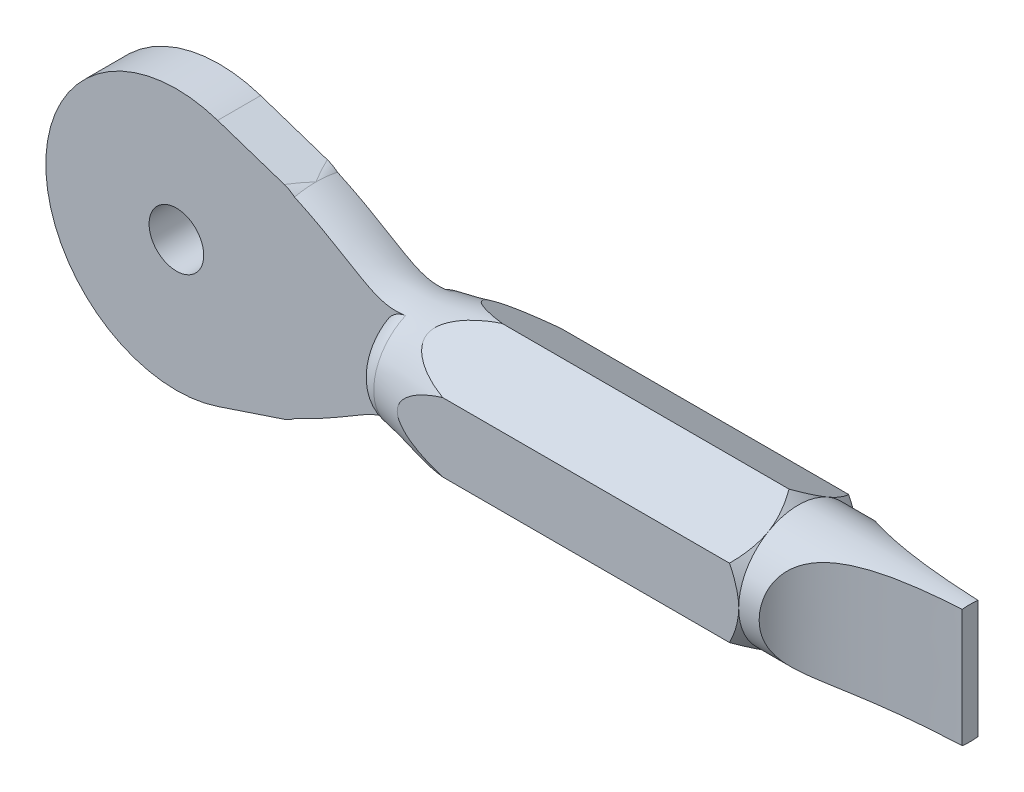
SolidWorks part; units mm, degrees
ref_plane "Front Plane" through (0, 0, 0) normal (0, 0, 1) x (1, 0, 0)
ref_plane "Top Plane" through (0, 0, 0) normal (0, 1, 0) x (1, 0, 0)
ref_plane "Right Plane" through (0, 0, 0) normal (1, 0, 0) x (0, 0, -1)
sketch "Sketch1" plane through (0, 0, 0) normal (1, 0, 0) x (0, 0, -1)
  line L1 (0, -40) -> (34.641, -20)
  line L2 (34.641, -20) -> (34.641, 20)
  line L3 (34.641, 20) -> (0, 40)
  line L4 (0, 40) -> (-34.641, 20)
  line L5 (-34.641, 20) -> (-34.641, -20)
  line L6 (-34.641, -20) -> (0, -40)
  circle A0 centre (0, 0) radius 34.641 construction
  dimension "D1" = 40
extrude "Boss-Extrude1" add sketch "Sketch1" along normal blind 229
sketch "Sketch2" plane through (229, 0, 0) normal (1, 0, 0) x (0, 0, -1)
  circle A0 centre (0, 0) radius 34.641
extrude "Cut-Extrude1" cut sketch "Sketch2" against normal blind 229 draft 45 flip side to cut
sketch "Sketch3" plane through (229, 0, 0) normal (1, 0, 0) x (0, 0, -1)
  arc A0 (-34.641, 0) -> (-17.3205, -30) centre (0, 0) ccw construction
  arc A1 (-17.3205, -30) -> (17.3205, -30) centre (0, 0) ccw construction
  arc A2 (17.3205, -30) -> (34.641, 0) centre (0, 0) ccw construction
  arc A3 (34.641, 0) -> (17.3205, 30) centre (0, 0) ccw construction
  arc A4 (17.3205, 30) -> (-17.3205, 30) centre (0, 0) ccw construction
  arc A5 (-17.3205, 30) -> (-34.641, 0) centre (0, 0) ccw construction
  arc A6 (-34.641, 0) -> (-17.3205, -30) centre (0, 0) ccw
  arc A7 (-17.3205, -30) -> (17.3205, -30) centre (0, 0) ccw
  arc A8 (17.3205, -30) -> (34.641, 0) centre (0, 0) ccw
  arc A9 (34.641, 0) -> (17.3205, 30) centre (0, 0) ccw
  arc A10 (17.3205, 30) -> (-17.3205, 30) centre (0, 0) ccw
  arc A11 (-17.3205, 30) -> (-34.641, 0) centre (0, 0) ccw
extrude "Boss-Extrude2" add sketch "Sketch3" along normal blind 100
sketch "Sketch4" plane through (0, 0, 0) normal (0, 1, 0) x (1, 0, 0)
  line L0 (0, 0) -> (378.2158, 0) construction
  line L1 (329, 34.641) -> (229, 34.641) construction
  line L2 (240.9158, 34.641) -> (366.1191, 34.641)
  line L3 (366.1191, 34.641) -> (371.6312, 3.0939)
  line L4 (240.9158, -34.641) -> (366.1191, -34.641)
  line L5 (366.1191, -34.641) -> (371.6312, -3.0939)
  spline S0 degree 3 poles (240.9158, 34.641) (256.6088, 2.3745) (332.2036, 4.8558) (371.6312, 3.0939) knots 0 0 0 0 1 1 1 1
  spline S1 degree 3 poles (240.9158, -34.641) (256.6088, -2.3745) (332.2036, -4.8558) (371.6312, -3.0939) knots 0 0 0 0 1 1 1 1
extrude "Cut-Extrude2" cut sketch "Sketch4" against normal mid plane 100
sketch "Sketch5" plane through (0, 0, 0) normal (0, 0, 1) x (1, 0, 0)
  line L0 (-96.2269, 72.0698) -> (0, 40)
  line L1 (-96.2269, -72.0698) -> (0, -40)
  line L2 (0, -40) -> (0, 40)
  circle A0 centre (-120.2458, 0) radius 15.8933
  arc A1 (-96.2269, 72.0698) -> (-96.2269, -72.0698) centre (-120.2458, 0) ccw
extrude "Boss-Extrude3" add sketch "Sketch5" along normal mid plane 25
sketch "Sketch6" plane through (0, 0, 0) normal (0, 0, 1) x (1, 0, 0)
  line L0 (0, 40) -> (-96.2269, 72.0698) construction
  line L1 (223.641, 40) -> (0, 40) construction
  line L3 (-121.7726, 0) -> (112.3775, 0) construction
  spline S0 degree 3 poles (-51.5345, 57.175) (-21.3156, 43.5974) (0.2128, 22.0547) (30.5967, 36.0182) (56.7699, 40) knots 0 0 0 0 0.537792 1 1 1 1
  spline S1 degree 2 poles (-51.5345, 57.175) (-50.3653, 130.1234) (56.7699, 40) knots 0 0 0 1 1 1
revolve "Cut-Revolve1" cut sketch "Sketch6" angle 360 about L3
fillet "Fillet1" radius 15 2 edges at (0, 0, -31.4421) (0, 0, 31.4421)
fillet "Fillet2" radius 15 4 edges
